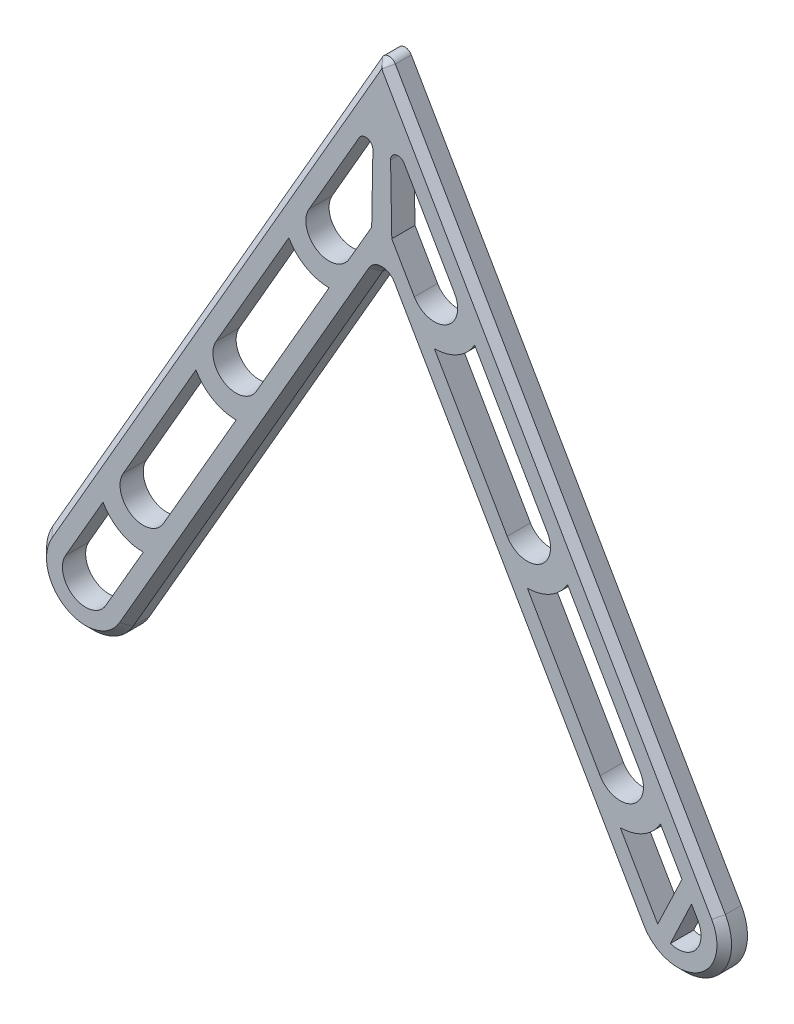
SolidWorks part; units mm, degrees
ref_plane "Front Plane" through (0, 0, 0) normal (0, 0, 1) x (1, 0, 0)
ref_plane "Top Plane" through (0, 0, 0) normal (0, 1, 0) x (1, 0, 0)
ref_plane "Right Plane" through (0, 0, 0) normal (1, 0, 0) x (0, 0, -1)
sketch "Sketch1" plane through (0, 0, 0) normal (0, 0, 1) x (1, 0, 0)
  line L0 (0, 0) -> (-45.974, -79.6293)
  line L1 (0, 0) -> (0, -82.5912) construction
  line L2 (0, -25.4) -> (-34.9755, -85.9793)
  line L3 (-1.139, -8.3228) -> (-9.9504, -23.5845)
  line L4 (10.9985, -6.35) -> (-39.8015, -94.3382) construction
  line L5 (-2.7496, -23.8125) -> (-4.4511, -26.7595)
  line L6 (-45.3007, -91.1632) -> (0, -12.7) construction
  line L7 (-38.1, -65.9911) -> (-27.1015, -72.3411) construction
  line L8 (-38.1, -72.3411) -> (-43.2244, -81.2168)
  line L9 (-32.6007, -75.5161) -> (-37.7251, -84.3918)
  line L10 (2.7496, -1.5875) -> (-48.0504, -89.5757) construction
  line L11 (-19.9007, -53.5191) -> (-29.8511, -70.7536)
  line L12 (-2.7496, -23.8125) -> (-42.5511, -92.7507) construction
  line L13 (-25.4, -50.3441) -> (-35.3504, -67.5786)
  line L14 (-7.2007, -31.522) -> (-17.1511, -48.7566)
  line L15 (-12.7, -28.347) -> (-22.6504, -45.5816)
  line L16 (-2.7496, -23.8125) -> (-1.3748, -21.4312)
  line L17 (38.1, -65.9911) -> (27.1015, -72.3411) construction
  line L18 (45.3007, -91.1632) -> (0, -12.7) construction
  line L19 (2.7496, -23.8125) -> (1.3748, -21.4312)
  line L20 (12.7, -28.347) -> (22.6504, -45.5816)
  line L21 (7.2007, -31.522) -> (17.1511, -48.7566)
  line L22 (25.4, -50.3441) -> (35.3504, -67.5786)
  line L23 (19.9007, -53.5191) -> (29.8511, -70.7536)
  line L24 (32.6007, -75.5161) -> (37.7251, -84.3918)
  line L25 (38.1, -72.3411) -> (41.0417, -77.4364)
  line L26 (2.7496, -23.8125) -> (4.4511, -26.7595)
  line L27 (1.139, -8.3228) -> (9.9504, -23.5845)
  line L28 (0, -25.4) -> (34.9755, -85.9793)
  line L29 (0, 0) -> (45.974, -79.6293)
  line L30 (-1.139, -8.3228) -> (-1.3748, -21.4312)
  line L31 (1.139, -8.3228) -> (1.3748, -21.4312)
  line L37 (39.5101, -85.7097) -> (42.2667, -79.8719)
  line L38 (0, 0) -> (-50.8, -87.9882) construction
  line L39 (0, -25.4) -> (-39.8015, -94.3382) construction
  line L40 (37.7251, -84.3918) -> (41.0417, -77.4364)
  line L41 (42.3482, -79.6993) -> (43.2244, -81.2168)
  line L42 (42.2667, -79.8719) -> (42.3482, -79.6993)
  line L43 (39.5101, -85.7097) -> (39.4612, -85.8132)
  arc A0 (34.9755, -85.9793) -> (45.974, -79.6293) centre (40.4747, -82.8043) ccw
  arc A1 (39.4612, -85.8132) -> (43.2244, -81.2168) centre (40.4747, -82.8043) ccw
  arc A2 (-35.3504, -67.5786) -> (-29.8511, -70.7536) centre (-32.6007, -69.1661) ccw
  arc A3 (-38.1, -72.3411) -> (-32.6007, -75.5161) centre (-32.6007, -69.1661) ccw
  arc A4 (-25.4, -50.3441) -> (-19.9007, -53.5191) centre (-19.9007, -47.1691) ccw
  arc A5 (-38.1, -65.9911) -> (-27.1015, -72.3411) centre (-32.6007, -69.1661) ccw construction
  arc A6 (-22.6504, -45.5816) -> (-17.1511, -48.7566) centre (-19.9007, -47.1691) ccw
  arc A7 (-12.7, -28.347) -> (-7.2007, -31.522) centre (-7.2007, -25.172) ccw
  arc A8 (-9.9504, -23.5845) -> (-4.4511, -26.7595) centre (-7.2007, -25.172) ccw
  arc A9 (9.9504, -23.5845) -> (4.4511, -26.7595) centre (7.2007, -25.172) cw
  arc A10 (12.7, -28.347) -> (7.2007, -31.522) centre (7.2007, -25.172) cw
  arc A11 (22.6504, -45.5816) -> (17.1511, -48.7566) centre (19.9007, -47.1691) cw
  arc A12 (25.4, -50.3441) -> (19.9007, -53.5191) centre (19.9007, -47.1691) cw
  arc A13 (38.1, -72.3411) -> (32.6007, -75.5161) centre (32.6007, -69.1661) cw
  arc A14 (35.3504, -67.5786) -> (29.8511, -70.7536) centre (32.6007, -69.1661) cw
  arc A17 (-37.7251, -84.3918) -> (-43.2244, -81.2168) centre (-40.4747, -82.8043) cw
  arc A18 (-34.9755, -85.9793) -> (-45.974, -79.6293) centre (-40.4747, -82.8043) cw
  arc A19 (-39.8015, -94.3382) -> (-50.8, -87.9882) centre (-45.3007, -91.1632) cw construction
  arc A20 (-42.5511, -92.7507) -> (-48.0504, -89.5757) centre (-45.3007, -91.1632) cw construction
  point P24 (41.9693, -91.645)
  point P72 (43.8425, -87.6781)
  dimension "D2" = 30
  dimension "D5" = 25.4
  dimension "D3" = 12.7
  dimension "D4" = 3.175
  dimension "D6" = 3.175
  dimension "D7" = 3
extrude "Boss-Extrude1" add sketch "Sketch1" along normal blind 3.175
fillet "Fillet1" radius 1 3 edges at (-1.139, -8.3228, 1.5875) (1.139, -8.3228, 1.5875) (0, 0, 1.5875)
fillet "Fillet2" radius 1 1 edges at (0, -25.4, 1.5875)
chamfer "Chamfer1" distance 1 angle 45 8 edges at (43.6497, -88.3036, 3.175) (23.42, -40.5647, 3.175) (0, -1, 3.175) (-23.42, -40.5647, 3.175) (-43.6497, -88.3036, 3.175) (17.9208, -56.4397, 3.175) (0, -26.4, 3.175) (-17.9208, -56.4397, 3.175)
